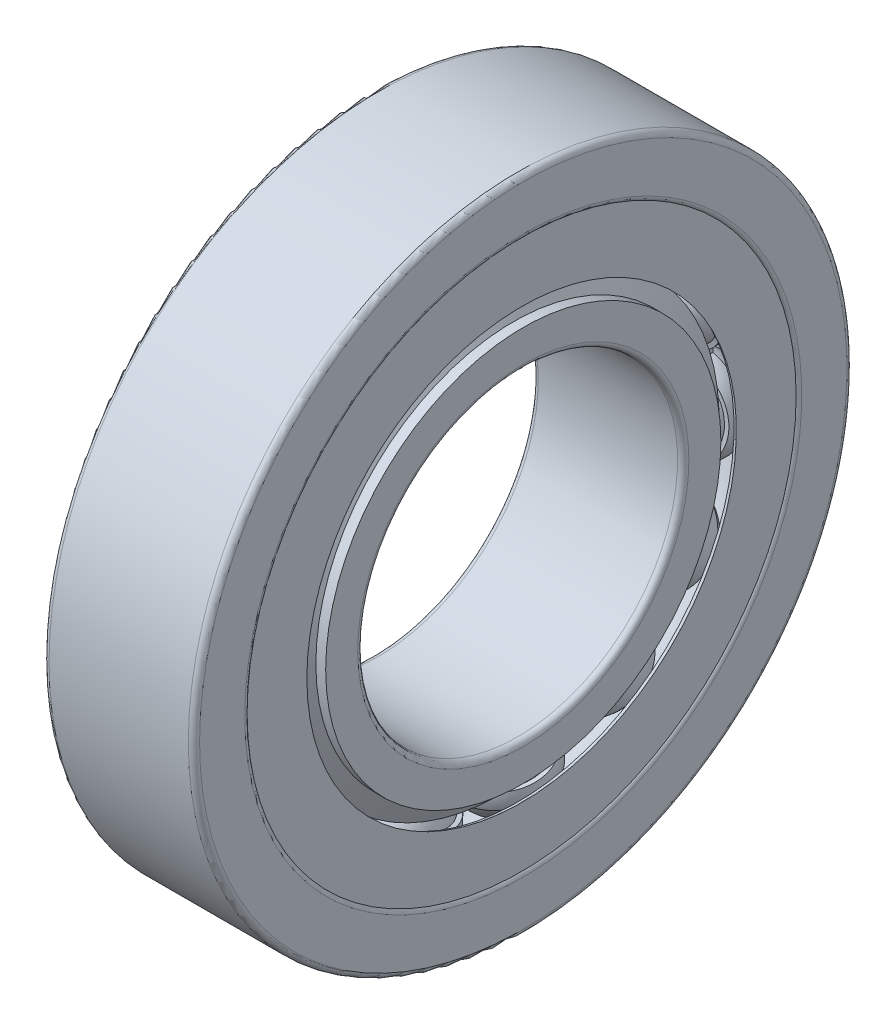
SolidWorks part; units mm, degrees
ref_plane "前视基准面" through (0, 0, 0) normal (0, 0, 1) x (1, 0, 0)
ref_plane "上视基准面" through (0, 0, 0) normal (0, 1, 0) x (1, 0, 0)
ref_plane "右视基准面" through (0, 0, 0) normal (1, 0, 0) x (0, 0, -1)
sketch "尺寸草图" plane through (0, 0, 0) normal (0, 0, 1) x (1, 0, 0)
  line L0 (-19.9271, 0) -> (19.9271, 0) construction
  line L1 (0, 21.603) -> (0, -21.603) construction
  line L2 (-3.7, 17.5) -> (3.7, 17.5)
  line L3 (4, 17.2) -> (4, 14.8)
  line L4 (-4, 17.2) -> (-4, 14.8)
  line L5 (-3.7, 14.5) -> (3.7, 14.5)
  line L6 (-3.5, 13) -> (3.3577, 13) construction
  line L7 (-3.7, 11.5) -> (3.7, 11.5)
  line L8 (4, 11.2) -> (4, 8.8)
  line L9 (3.7, 8.5) -> (-3.7, 8.5)
  line L10 (-4, 8.8) -> (-4, 11.2)
  line L11 (0, 13) -> (0, 15.25) construction
  line L13 (3.7, 14.5) -> (3.7, 11.5)
  line L14 (2.9, 11.5) -> (3.4774, 10.5)
  line L15 (3.4774, 10.5) -> (4, 10.5)
  line L16 (3.9121, 14.5879) -> (3.9121, 11.4121)
  circle A0 centre (0, 13) radius 2.25
  arc A1 (4, 14.8) -> (3.7, 14.5) centre (3.7, 14.8) cw
  arc A2 (4, 11.2) -> (3.7, 11.5) centre (3.7, 11.2) ccw
  arc A3 (-3.7, 11.5) -> (-4, 11.2) centre (-3.7, 11.2) ccw
  arc A4 (-3.7, 14.5) -> (-4, 14.8) centre (-3.7, 14.8) cw
  arc A5 (-3.7, 8.5) -> (-4, 8.8) centre (-3.7, 8.8) cw
  arc A6 (3.7, 8.5) -> (4, 8.8) centre (3.7, 8.8) ccw
  arc A7 (4, 17.2) -> (3.7, 17.5) centre (3.7, 17.2) ccw
  arc A8 (-3.7, 17.5) -> (-4, 17.2) centre (-3.7, 17.2) ccw
  point P7 (0, 0)
  point P25 (-4, 11.5)
  point P28 (-4, 14.5)
  point P31 (-4, 8.5)
  point P36 (4, 17.5)
  point P39 (-4, 17.5)
  dimension "D1" = 0.75
  dimension "D3" = 0.3
  dimension "B" = 8
  dimension "D2" = 4
  dimension "D" = 35
  dimension "(d)" = 17
  dimension "D5" = 13
  dimension "D6" = 3
  dimension "D7" = 3
  dimension "D8" = 1
  dimension "D9" = 60
  dimension "D10" = 1.1
sketch "草图2" plane through (0, 0, 0) normal (0, 0, 1) x (1, 0, 0)
  line L0 (2.9, 11.5) -> (3.4774, 10.5) construction
  line L1 (3.4774, 10.5) -> (4, 10.5) construction
  line L2 (2.9, 11.5) -> (3.4774, 10.5)
  line L3 (3.4774, 10.5) -> (4, 10.5)
  line L4 (0, 15.25) -> (0, 10.75) construction
  line L5 (-3.4774, 10.5) -> (-4, 10.5)
  line L6 (3.7, 8.5) -> (-3.7, 8.5) construction
  line L7 (-2.9, 11.5) -> (-3.4774, 10.5)
  line L8 (-4, 17.2) -> (-4, 14.8) construction
  line L9 (-3.7, 14.5) -> (3.7, 14.5) construction
  line L10 (-3.7, 17.5) -> (3.7, 17.5) construction
  line L11 (4, 17.2) -> (4, 14.8) construction
  line L12 (4, 11.2) -> (4, 8.8) construction
  line L13 (-3.7, 11.5) -> (3.7, 11.5) construction
  line L14 (3.7, 8.5) -> (-3.7, 8.5)
  line L15 (-4, 8.8) -> (-4, 11.2) construction
  line L18 (-3.5, 0) -> (3.5, 0) construction
  line L19 (-19.9271, 0) -> (19.9271, 0) construction
  line L20 (-4, 17.2) -> (-4, 14.8)
  line L21 (-3.7, 14.5) -> (-1.6771, 14.5)
  line L22 (-3.7, 17.5) -> (3.7, 17.5)
  line L23 (4, 17.2) -> (4, 14.8)
  line L24 (4, 10.5) -> (4, 8.8)
  line L25 (-2.9, 11.5) -> (-1.6771, 11.5)
  line L26 (-4, 8.8) -> (-4, 10.5)
  line L27 (1.6771, 14.5) -> (3.7, 14.5)
  line L28 (1.6771, 11.5) -> (2.9, 11.5)
  circle A0 centre (0, 13) radius 2.25 construction
  arc A1 (1.6771, 14.5) -> (-1.6771, 14.5) centre (0, 13) ccw
  arc A2 (-1.6771, 11.5) -> (1.6771, 11.5) centre (0, 13) ccw
  arc A3 (-3.7, 17.5) -> (-4, 17.2) centre (-3.7, 17.2) ccw construction
  arc A4 (-4, 14.8) -> (-3.7, 14.5) centre (-3.7, 14.8) ccw construction
  arc A5 (4, 17.2) -> (3.7, 17.5) centre (3.7, 17.2) ccw construction
  arc A6 (3.7, 14.5) -> (4, 14.8) centre (3.7, 14.8) ccw construction
  arc A8 (3.7, 8.5) -> (4, 8.8) centre (3.7, 8.8) ccw construction
  arc A10 (-4, 8.8) -> (-3.7, 8.5) centre (-3.7, 8.8) ccw construction
  arc A11 (-3.7, 17.5) -> (-4, 17.2) centre (-3.7, 17.2) ccw
  arc A12 (-4, 14.8) -> (-3.7, 14.5) centre (-3.7, 14.8) ccw
  arc A13 (4, 17.2) -> (3.7, 17.5) centre (3.7, 17.2) ccw
  arc A14 (3.7, 14.5) -> (4, 14.8) centre (3.7, 14.8) ccw
  arc A16 (3.7, 8.5) -> (4, 8.8) centre (3.7, 8.8) ccw
  arc A18 (-4, 8.8) -> (-3.7, 8.5) centre (-3.7, 8.8) ccw
revolve "旋转1" add sketch "草图2" angle 360 about L18
sketch "草图5" plane through (0, 0, 0) normal (0, 0, 1) x (1, 0, 0)
  line L1 (-0.675, 12.55) -> (0.675, 12.55)
  line L2 (-0.675, 12.55) -> (-0.675, 13.45)
  line L3 (-0.675, 13.45) -> (0.675, 13.45)
  line L4 (0.675, 12.55) -> (0.675, 13.45)
  line L5 (-0.675, 12.55) -> (0.675, 13.45) construction
  line L6 (-0.675, 13.45) -> (0.675, 12.55) construction
  circle A0 centre (0, 13) radius 2.25 construction
  circle A1 centre (0, 13) radius 2.25 construction
  point P0 (0, 13)
  dimension "D3" = 4.5
  dimension "D1" = 1.35
  dimension "D2" = 0.9
revolve "旋转3" add sketch "草图5" angle 360 about L0
sketch "草图3" plane through (0, 0, 0) normal (0, 0, 1) x (1, 0, 0)
  line L1 (-2.475, 13) -> (2.475, 13)
  circle A0 centre (0, 13) radius 2.25 construction
  circle A1 centre (0, 13) radius 2.25 construction
  arc A2 (2.475, 13) -> (-2.475, 13) centre (0, 13) ccw
  dimension "D2" = 4.95
revolve "旋转2" add sketch "草图3" angle 360 about L1 region at (0, 14.0504, 0)
ref_axis "基准轴1" through (-3.85, 0, 0) along (1, 0, 0)
pattern_circular "阵列(圆周)5" count 15 over 360 about axis through (-3.85, 0, 0) along (1, 0, 0) of bodies 103
sketch "草图6" plane through (0, 0, 0) normal (0, 0, 1) x (1, 0, 0)
  line L0 (-2.4337, 13.45) -> (2.4337, 13.45)
  line L1 (-3.5, 13) -> (4, 13) construction
  line L3 (-2.4337, 12.55) -> (2.4337, 12.55)
  line L4 (4, -17.2) -> (4, 17.2) construction
  arc A0 (-2.4337, 12.55) -> (2.4337, 12.55) centre (0, 13) ccw
  circle A1 centre (0, 13) radius 2.25 construction
  circle A2 centre (0, 13) radius 2.25 construction
  arc A3 (2.4337, 13.45) -> (-2.4337, 13.45) centre (0, 13) ccw
  dimension "D1" = 4.95
  dimension "D2" = 4.5
  dimension "D3" = 0.45
  dimension "D4" = 0.45
revolve "切除-旋转1" cut sketch "草图6" angle 360 about L0
sketch "草图7" plane through (0, 0, 0) normal (0, 0, 1) x (1, 0, 0)
  line L0 (-2.25, 13) -> (2.25, 13)
  line L1 (-4, 0) -> (2.4587, 0) construction
  line L2 (-4, 17.2) -> (-4, -17.2) construction
  line L3 (-19.9271, 0) -> (19.9271, 0) construction
  circle A0 centre (0, 13) radius 2.25 construction
  arc A1 (2.25, 13) -> (-2.25, 13) centre (0, 13) ccw
revolve "旋转4" add sketch "草图7" angle 360 about L0
pattern_circular "阵列(圆周)2" count 15 over 360 about axis through (-3.85, 0, 0) along (1, 0, 0) of "旋转4" reverse direction yes
sketch "草图9" plane through (0, 0, 0) normal (0, 0, 1) x (1, 0, 0)
  line L1 (3.7, 14.5) -> (3.7, 11.5) construction
  line L4 (3.9121, 14.5879) -> (3.9121, 11.4121) construction
  line L5 (3.7, 14.5) -> (3.7, 11.5)
  line L6 (3.9121, 14.5879) -> (3.9121, 11.4121)
  line L7 (-3.9121, 14.5879) -> (-3.9121, 11.4121)
  line L8 (0, 17.5) -> (0, 0) construction
  line L9 (-3.7, 17.5) -> (3.7, 17.5) construction
  line L10 (-3.7, 14.5) -> (-3.7, 11.5)
  arc A0 (3.7, 14.5) -> (4, 14.8) centre (3.7, 14.8) ccw construction
  arc A1 (3.7, 14.5) -> (3.9121, 14.5879) centre (3.7, 14.8) ccw
  arc A2 (4, 11.2) -> (3.7, 11.5) centre (3.7, 11.2) ccw construction
  arc A3 (3.9121, 11.4121) -> (3.7, 11.5) centre (3.7, 11.2) ccw
  arc A4 (-3.9121, 11.4121) -> (-3.7, 11.5) centre (-3.7, 11.2) cw
  arc A5 (-3.7, 14.5) -> (-3.9121, 14.5879) centre (-3.7, 14.8) cw
revolve "旋转5" add sketch "草图9" angle 360 about L0
